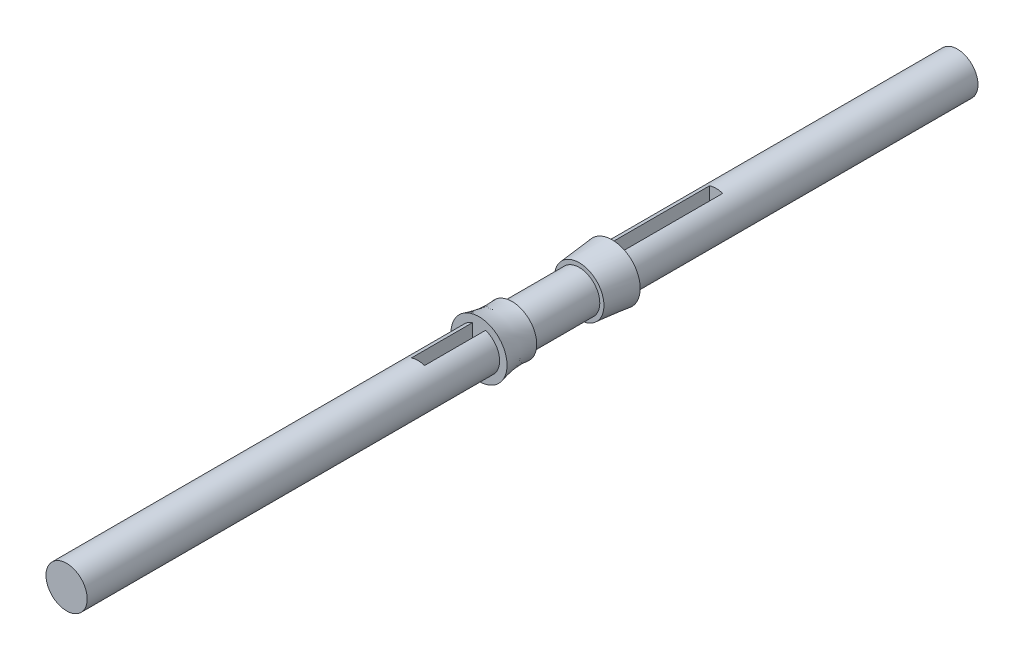
SolidWorks part; units mm, degrees
ref_plane "Front Plane" through (0, 0, 0) normal (0, 0, 1) x (1, 0, 0)
ref_plane "Top Plane" through (0, 0, 0) normal (0, 1, 0) x (1, 0, 0)
ref_plane "Right Plane" through (0, 0, 0) normal (1, 0, 0) x (0, 0, -1)
sketch "Sketch1" plane through (0, 0, 0) normal (0, 0, 1) x (1, 0, 0)
  circle A0 centre (0, 0) radius 12.5
extrude "Boss-Extrude1" add sketch "Sketch1" along normal blind 500
ref_plane "Plane1" through (0, 0, 209.275) normal (0, 0, 1) x (1, 0, 0)
sketch "Sketch2" plane through (0, 0, 209.275) normal (0, 0, 1) x (1, 0, 0)
  circle A0 centre (0, 0) radius 17
ref_plane "Plane2" through (0, 0, 229.275) normal (0, 0, 1) x (1, 0, 0)
sketch "Sketch3" plane through (0, 0, 229.275) normal (0, 0, 1) x (1, 0, 0)
  circle A0 centre (0, 0) radius 15
loft "Loft1" add profiles "Sketch3", "Sketch2" connector at (12.2123, -8.7097, 229.275) connector at (11.0812, -12.8922, 209.275)
ref_plane "Plane3" through (0, 0, 270) normal (0, 0, 1) x (1, 0, 0)
sketch "Sketch4" plane through (0, 0, 270) normal (0, 0, 1) x (1, 0, 0)
  circle A0 centre (0, 0) radius 15
ref_plane "Plane4" through (0, 0, 290) normal (0, 0, 1) x (1, 0, 0)
sketch "Sketch5" plane through (0, 0, 290) normal (0, 0, 1) x (1, 0, 0)
  circle A0 centre (0, 0) radius 17
loft "Loft2" add profiles "Sketch5", "Sketch4" connector at (-16.9205, -1.6424, 290) connector at (-12.1353, 8.8168, 270)
sketch "Sketch6" plane through (0, 0, 500) normal (0, 0, 1) x (1, 0, 0)
  circle A0 centre (0, 0) radius 12.5
extrude "Boss-Extrude2" add sketch "Sketch6" along normal blind 40
sketch "Sketch7" plane through (0, 0, 0) normal (0, 0, -1) x (-1, 0, 0)
  circle A0 centre (0, 0) radius 12.4992
ref_plane "Plane5" through (0, 12.5, 0) normal (0, 1, 0) x (1, 0, 0)
sketch "Sketch8" plane through (0, 12.5, 0) normal (0, 1, 0) x (1, 0, 0)
  line L0 (-12.5, -290) -> (12.5, -290)
  line L1 (0, -290) -> (-4, -290)
  line L2 (-4, -290) -> (4, -290)
  line L3 (4, -290) -> (4, -327)
  line L4 (4, -327) -> (-4, -327)
  line L5 (-4, -327) -> (-4, -290)
sketch "Sketch9" plane through (0, 12.5, 0) normal (0, 1, 0) x (1, 0, 0)
  line L0 (-12.5, -209.275) -> (12.5, -209.275)
  line L1 (0, -209.275) -> (4, -209.275)
  line L2 (4, -209.275) -> (-4, -209.275)
  line L3 (-4, -209.275) -> (-4, -146.275)
  line L4 (-4, -146.275) -> (4, -146.275)
  line L5 (4, -146.275) -> (4, -209.275)
  dimension "D1" = 8
  dimension "D2" = 4
extrude "Cut-Extrude1" cut sketch "Sketch9" against normal blind 10 contours L5 L4 L3 L0 region at (0, 12.5, 177.775)
extrude "Cut-Extrude2" cut sketch "Sketch8" against normal blind 10 contours L2 L3 L4 L5
